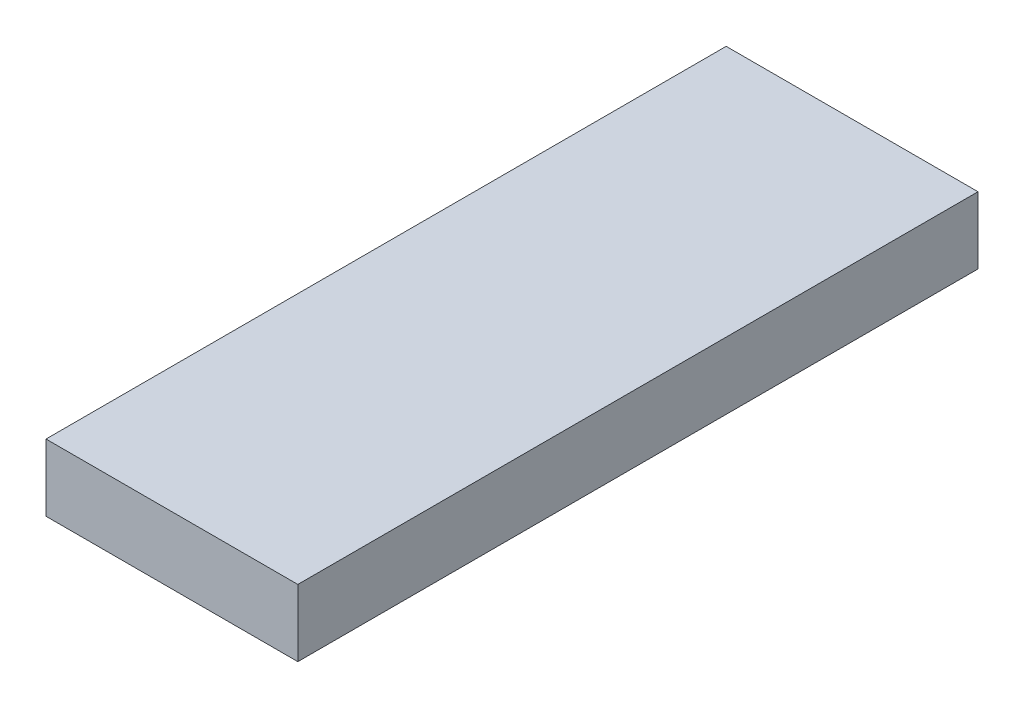
SolidWorks part; units mm, degrees
material "Copper"
ref_plane "Front Plane" through (0, 0, 0) normal (0, 0, 1) x (1, 0, 0)
ref_plane "Top Plane" through (0, 0, 0) normal (0, 1, 0) x (1, 0, 0)
ref_plane "Right Plane" through (0, 0, 0) normal (1, 0, 0) x (0, 0, -1)
sketch "Sketch1" plane through (0, 0, 0) normal (0, 0, 1) x (1, 0, 0)
  line L4 (-5.6462, 53.7197) -> (-5.6462, 56.7197)
  line L5 (27.0078, 46.7789) -> (16.6917, 51.3719)
  line L6 (16.6917, 51.3719) -> (5.6462, 53.7197)
  line L7 (5.6462, 53.7197) -> (-5.6462, 53.7197)
  line L8 (-5.6462, 53.7197) -> (-16.6917, 51.3719)
  line L9 (-16.6917, 51.3719) -> (-27.0078, 46.7789)
  line L10 (-27.0078, 46.7789) -> (-36.1435, 40.1414)
  line L11 (-36.1435, 40.1414) -> (-43.6995, 31.7496)
  line L12 (-43.6995, 31.7496) -> (-49.3457, 21.9701)
  line L13 (-49.3457, 21.9701) -> (-52.8352, 11.2305)
  line L14 (-52.8352, 11.2305) -> (-54.0156, 0)
  line L15 (-54.0156, 0) -> (-52.8352, -11.2305)
  line L16 (-52.8352, -11.2305) -> (-49.3457, -21.9701)
  line L17 (-49.3457, -21.9701) -> (-43.6995, -31.7496)
  line L18 (-43.6995, -31.7496) -> (-36.1435, -40.1414)
  line L19 (-36.1435, -40.1414) -> (-27.0078, -46.7789)
  line L20 (-27.0078, -46.7789) -> (-16.6917, -51.3719)
  line L21 (-16.6917, -51.3719) -> (-5.6462, -53.7197)
  line L22 (-5.6462, -53.7197) -> (5.6462, -53.7197)
  line L23 (5.6462, -53.7197) -> (16.6917, -51.3719)
  line L24 (16.6917, -51.3719) -> (27.0078, -46.7789)
  line L25 (27.0078, -46.7789) -> (36.1435, -40.1414)
  line L26 (36.1435, -40.1414) -> (43.6995, -31.7496)
  line L27 (43.6995, -31.7496) -> (49.3457, -21.9701)
  line L28 (49.3457, -21.9701) -> (52.8352, -11.2305)
  line L29 (52.8352, -11.2305) -> (54.0156, 0)
  line L30 (54.0156, 0) -> (52.8352, 11.2305)
  line L31 (52.8352, 11.2305) -> (49.3457, 21.9701)
  line L32 (49.3457, 21.9701) -> (43.6995, 31.7496)
  line L33 (43.6995, 31.7496) -> (36.1435, 40.1414)
  line L34 (36.1435, 40.1414) -> (27.0078, 46.7789)
  line L35 (-5.6462, 56.7197) -> (5.6462, 56.7197)
  line L36 (5.6462, 56.7197) -> (5.6462, 53.7197)
  circle A1 centre (0, 0) radius 53.7197 construction
  dimension "D1" = 3
  dimension "D2" = 57
extrude "Boss-Extrude1" add sketch "Sketch1" along normal mid plane 30.5 contours L36 L35 L4 L7 region at (0, 55.2197, 0)
